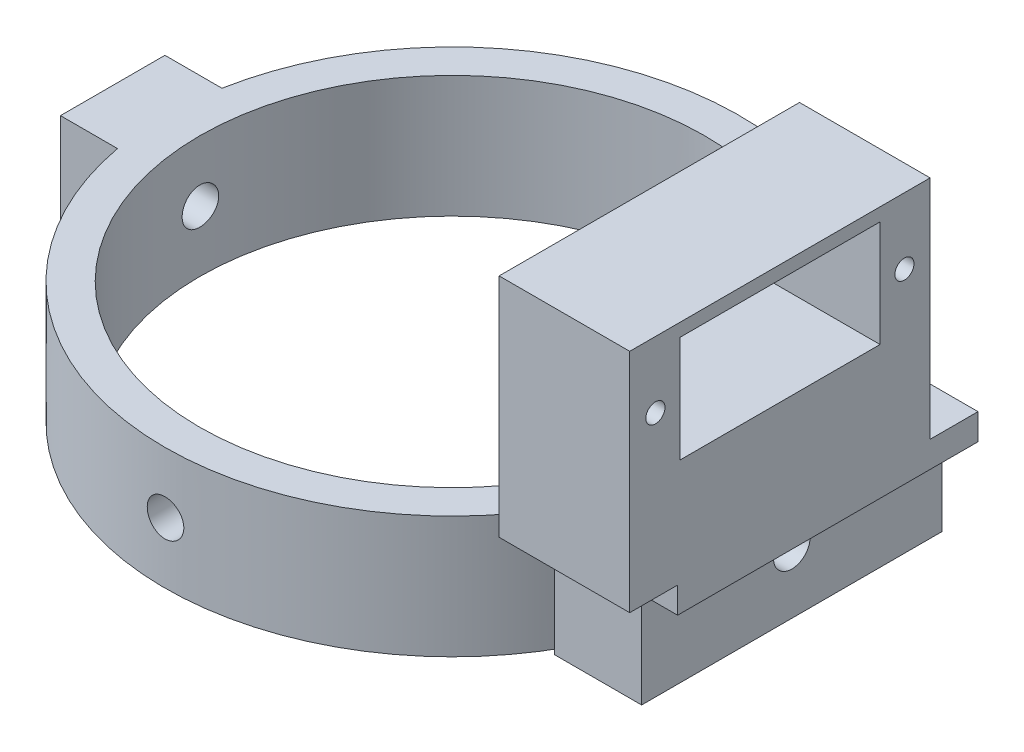
SolidWorks part; units mm, degrees
ref_plane "Front Plane" through (0, 0, 0) normal (0, 0, 1) x (1, 0, 0)
ref_plane "Top Plane" through (0, 0, 0) normal (0, 1, 0) x (1, 0, 0)
ref_plane "Right Plane" through (0, 0, 0) normal (1, 0, 0) x (0, 0, -1)
sketch "Sketch1" plane through (0, 0, 0) normal (0, 1, 0) x (1, 0, 0)
  circle A0 centre (0, 0) radius 29
  circle A1 centre (0, 0) radius 33
  dimension "D1" = 58
  dimension "D2" = 66
extrude "Boss-Extrude1" add sketch "Sketch1" along normal mid plane 14
sketch "Sketch2" plane through (0, 0, 0) normal (0, 1, 0) x (1, 0, 0)
  line L9 (29, -17.25) -> (39, -17.25)
  line L10 (29, -17.25) -> (29, 17.25)
  line L11 (29, 17.25) -> (39, 17.25)
  line L12 (39, -17.25) -> (39, 17.25)
  line L13 (29, -17.25) -> (39, 17.25) construction
  line L14 (29, 17.25) -> (39, -17.25) construction
  line L15 (-29, -6) -> (-39, -6)
  line L16 (-29, -6) -> (-29, 6)
  line L17 (-29, 6) -> (-39, 6)
  line L18 (-39, -6) -> (-39, 6)
  line L19 (-29, -6) -> (-39, 6) construction
  line L20 (-29, 6) -> (-39, -6) construction
  circle A1 centre (0, 0) radius 29 construction
  point P0 (34, 0)
  point P8 (-34, 0)
  dimension "D1" = 12
  dimension "D2" = 10
  dimension "D3" = 10
  dimension "D4" = 34.5
extrude "Boss-Extrude2" add sketch "Sketch2" along normal mid plane 14
sketch "Sketch5" plane through (-39, 0, 0) normal (-1, 0, 0) x (0, 0, 1)
  circle A0 centre (0, 0) radius 2.1
  dimension "D1" = 4.2
extrude "Cut-Extrude1" cut sketch "Sketch5" against normal through all
sketch "Sketch7" plane through (0, 0, 0) normal (0, 0, 1) x (1, 0, 0)
  circle A0 centre (0, 0) radius 2.1
  dimension "D1" = 4.2
extrude "Cut-Extrude4" cut sketch "Sketch7" against normal blind 46.5 and the other way blind 36.5 contours A0
sketch "Sketch11" plane through (0, 0, 0) normal (0, 0, 1) x (1, 0, 0)
  line L0 (28.1325, 7) -> (28.1325, -7) construction
  line L1 (28.1325, 33) -> (43.1325, 33)
  line L2 (28.1325, 33) -> (28.1325, 7)
  line L3 (28.1325, 7) -> (43.1325, 7)
  line L4 (43.1325, 33) -> (43.1325, 7)
  line L5 (28.1325, 33) -> (43.1325, 7) construction
  line L6 (28.1325, 7) -> (43.1325, 33) construction
  line L7 (29, 7) -> (-29, 7) construction
  point P0 (35.6325, 20)
  point P9 (38.95, 5.5)
  point P14 (0, 0)
  dimension "D1" = 15
  dimension "D2" = 26
extrude "Boss-Extrude3" add sketch "Sketch11" along normal mid plane 34.5 from offset 5.5 contours L2 L1 L4 L3
sketch "Sketch12" plane through (0, 0, 0) normal (0, 0, 1) x (1, 0, 0)
  line L0 (28.1325, 7) -> (43.1325, 7) construction
  line L1 (29.0036, 7) -> (43.1325, 7)
  line L2 (29.0036, 7) -> (29.0036, 4)
  line L3 (29.0036, 4) -> (43.1325, 4)
  line L4 (43.1325, 7) -> (43.1325, 4)
  line L5 (29.0036, 7) -> (43.1325, 4) construction
  line L6 (29.0036, 4) -> (43.1325, 7) construction
  line L7 (43.1325, 33) -> (43.1325, 7) construction
  point P0 (36.068, 5.5)
  point P7 (0, 0)
  dimension "D1" = 3
extrude "Boss-Extrude4" add sketch "Sketch12" along normal mid plane 34.5
sketch "Sketch13" plane through (28.1325, 0, 0) normal (-1, 0, 0) x (0, 0, 1)
  line L0 (22.75, 33) -> (-11.75, 33) construction
  line L1 (-6, 31.5) -> (17, 31.5)
  line L2 (-6, 31.5) -> (-6, 19.3)
  line L3 (-6, 19.3) -> (17, 19.3)
  line L4 (17, 31.5) -> (17, 19.3)
  line L5 (-6, 31.5) -> (17, 19.3) construction
  line L6 (-6, 19.3) -> (17, 31.5) construction
  line L7 (22.75, 33) -> (22.75, 7) construction
  line L8 (7.0401, 7) -> (-7.0401, 7) construction
  circle A0 centre (-8.8, 25.4) radius 1.1
  circle A1 centre (19.8, 25.4) radius 1.1
  point P0 (5.5, 25.4)
  point P16 (0, 0)
  point P17 (0, 0)
  dimension "D5" = 2.2
  dimension "D6" = 2.2
  dimension "D1" = 23
  dimension "D2" = 12.2
  dimension "D3" = 1.5
  dimension "D4" = 5.75
  dimension "D7" = 2.8
  dimension "D8" = 2.8
  dimension "D9" = 12.3
extrude "Cut-Extrude5" cut sketch "Sketch13" against normal through all
